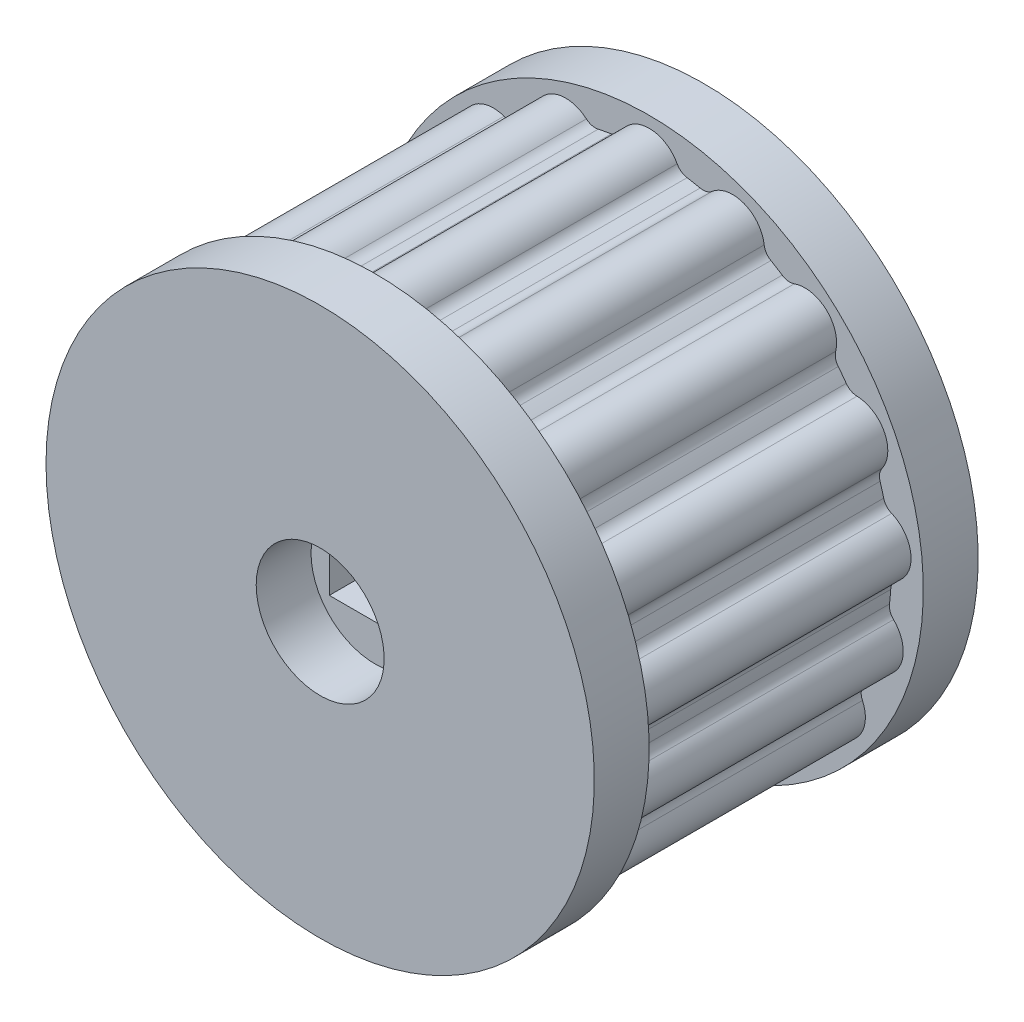
SolidWorks part; units mm, degrees
ref_plane "Plan de face" through (0, 0, 0) normal (0, 0, 1) x (1, 0, 0)
ref_plane "Plan de dessus" through (0, 0, 0) normal (0, 1, 0) x (1, 0, 0)
ref_plane "Plan de droite" through (0, 0, 0) normal (1, 0, 0) x (0, 0, -1)
sketch "Esquisse1" plane through (0, 0, 0) normal (0, 0, 1) x (1, 0, 0)
  line L0 (-2.5, 1.5) -> (2.5, 1.5)
  line L1 (-2.5, 1.5) -> (-2.5, -1.5)
  line L2 (-2.5, -1.5) -> (2.5, -1.5)
  line L3 (2.5, 1.5) -> (2.5, -1.5)
  circle A0 centre (0, 0) radius 15
  circle A1 centre (0, 0) radius 3.5
  point P7 (0, 1.5)
  point P8 (-2.5, 0)
  dimension "D1" = 30
  dimension "D2" = 5
  dimension "D3" = 3
extrude "Boss.-Extru.1" add sketch "Esquisse1" along normal blind 21 contours A0 A1 region at (-14.5757, 0, 0)
sketch "Esquisse2" plane through (0, 0, 0) normal (1, 0, 0) x (0, 0, -1)
  line L0 (0, 0) -> (-44, 0) construction
  line L1 (0, 0) -> (-22, 0)
  line L2 (-22, 0) -> (-22, 3.5)
  line L4 (-22, 3.5) -> (0, 3.5)
  line L6 (0, 3.5) -> (0, 0)
  point P5 (0, 0)
  point P6 (0, 0)
  point P7 (0, 0)
  point P12 (0, 0)
  dimension "D1" = 0
  dimension "D2" = 3.5
revolve "Enlèvement de matière-Révolution1" [suppressed] cut sketch "Esquisse2" angle 360 about L0
ref_plane "Plan1" through (0, 0, 3) normal (0, 0, -1) x (-1, 0, 0)
sketch "Esquisse3" plane through (0, 0, 3) normal (0, 0, -1) x (-1, 0, 0)
  circle A0 centre (0, 0) radius 13.2425
  circle A1 centre (0, 0) radius 28.5
  dimension "D1" = 26.485
extrude "Enlèv. mat.-Extru.1" cut sketch "Esquisse3" against normal blind 15
sketch "Esquisse5" plane through (0, 0, 3) normal (0, 0, 1) x (1, 0, 0)
  line L0 (0, 0) -> (0, 38.7923) construction
  line L1 (0, 38.7923) -> (-15.821, 13.2425) construction
  line L2 (-15.821, 13.2425) -> (15.2424, 13.2425) construction
  line L3 (-3.2223, 14.3825) -> (3.5661, 14.3825) construction
  circle A0 centre (0, 0) radius 13.2425 construction
  arc A1 (-1.6667, 13.1372) -> (1.6667, 13.1372) centre (0, 0) cw
  arc A2 (-1.6667, 13.1372) -> (1.6667, 13.1372) centre (0, 12.6445) cw
  dimension "D1" = 1.14
  dimension "D2" = 1.6667
extrude "Boss.-Extru.2" add sketch "Esquisse5" along normal up to surface (15 mm away) up to face at (-13.2425, 0, 18)
fillet "Congé1" radius 0.75 2 edges at (1.6667, 13.1372, 10.5) (-1.6667, 13.1372, 10.5)
pattern_circular "Répétition circulaire1" count 17 over 360 about axis through (0, 0, 3) along (0, 0, -1) of "Congé1", "Boss.-Extru.2"
extrude "Boss-Extrude1" add sketch "Esquisse1<3>" along normal mid plane 15 from offset 10.5 contours A1 L0 L3 L2 L1 region at (-3.401, 0, 0)
sketch "Esquisse1<3>" plane through (0, 0, 0) normal (0, 0, 1) x (1, 0, 0) same geometry as "Esquisse1"
